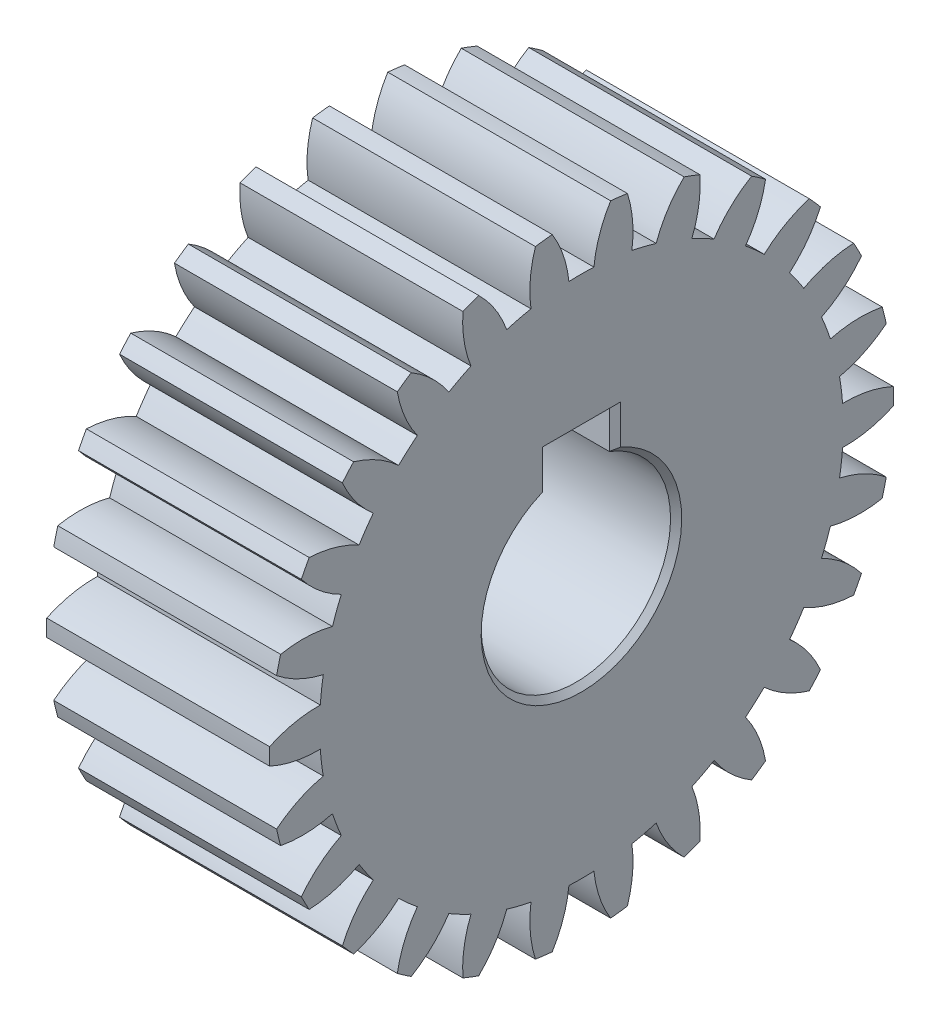
SolidWorks part; units mm, degrees
ref_plane "Plane1" through (0, 0, 0) normal (0, 0, 1) x (1, 0, 0)
ref_plane "Plane2" through (0, 0, 0) normal (0, 1, 0) x (1, 0, 0)
ref_plane "Plane3" through (0, 0, 0) normal (1, 0, 0) x (0, 0, -1)
sketch "HoldingSke" plane through (0, 0, 0) normal (0, 1, 0) x (1, 0, 0)
  line L0 (0, 0) -> (0.4494, -0.2192)
  line L1 (-15, 0) -> (100, 0) construction
  line L2 (0, 0) -> (-2.1039, 2.3779)
  line L3 (0, 0) -> (-11.863, 4.5341)
  line L4 (0, 0) -> (7.762, 3.7858)
  line L5 (0, 0) -> (-46.8476, -17.4728)
  line L6 (0, 0) -> (-16.5793, -11.1861)
  line L7 (-2.1039, 2.3779) -> (8.6586, 51.2059)
  line L8 (-76.2, 54.61) -> (-73.4, 54.61)
  line L9 (-67.7845, 28.3722) -> (-49.3413, 33.142)
  line L10 (-76.2, 71.12) -> (104.1128, 71.12)
  line L11 (0, 0) -> (-20, 0)
  line L12 (-76.2, 101.6) -> (-76.133, 101.6)
  line L13 (24.9733, 27.94) -> (52.9518, 28.4284)
  line L14 (24.9733, 27.94) -> (24.9743, 27.94)
  line L15 (24.9733, 27.94) -> (100.4006, 29.5858)
  line L16 (-63.627, -2) -> (-12.827, -2)
  circle A0 centre (0, 0) radius 8.5
  circle A1 centre (0, 0) radius 23.499
  circle A2 centre (0, 0) radius 37.5
  circle A3 centre (0, 0) radius 8.5
  dimension "Num_teeth" = 26
  dimension "Pitch_radius" = 180.3128
  dimension "Width" = 20
  dimension "Thickness" = 20
sketch "BasProSke" plane through (0, 0, 0) normal (0, 1, 0) x (1, 0, 0)
  line L0 (-10, 0) -> (60, 0) construction
  line L1 (0, 0) -> (0, 28)
  line L2 (0, 0) -> (20, 0)
  line L3 (20, 0) -> (20, 28)
  line L4 (20, 28) -> (0, 28)
  dimension "Thickness" = 20
  dimension "Diameter" = 56
revolve "Base-Revolve" add sketch "BasProSke" angle 360 about L0
sketch "TooCutSke" plane through (0, 0, 0) normal (1, 0, 0) x (0, 0, -1)
  line L1 (0, 0) -> (0, 107) construction
  line L2 (0, 0) -> (-1.6871, 25.9452) construction
  line L3 (0, 0) -> (-6.2581, 51.5402) construction
  line L4 (-1.6871, 25.9452) -> (-3.1291, 25.7701) construction
  arc A0 (1.1217, 23.4722) -> (-1.1217, 23.4722) centre (0, 0) ccw
  arc A1 (2.6361, 27.9012) -> (-2.6361, 27.9012) centre (0, 0) ccw
  circle A2 centre (0, 0) radius 26 construction
  circle A3 centre (0, 0) radius 25.1718 construction
  arc A4 (-1.1217, 23.4722) -> (-2.6361, 27.9012) centre (-11.4671, 22.4082) ccw
  arc A5 (2.6361, 27.9012) -> (1.1217, 23.4722) centre (11.4671, 22.4082) ccw
extrude "ToothCut" cut sketch "TooCutSke" along normal through all
fillet "Breaks" [suppressed] radius 0.04 tangent propagation no
fillet "RootFillets" [suppressed] radius 0.501
pattern_circular "TeethCuts" count 26 every 13.846 about axis through (-10, 0, 0) along (1, 0, 0) of "ToothCut", "RootFillets", "Breaks"
sketch "HubNeaOneSke" plane through (0, 0, 0) normal (-1, 0, 0) x (0, 0, 1)
  circle A0 centre (0, 0) radius 23.499
  dimension "Diameter" = 46.998
extrude "HubNearOne" [suppressed] add sketch "HubNeaOneSke" along normal blind 30.0001
sketch "HubNeaBotSke" plane through (0, 0, 0) normal (-1, 0, 0) x (0, 0, 1)
  circle A0 centre (0, 0) radius 23.499
  dimension "Diameter" = 46.998
extrude "HubNearBoth" [suppressed] add sketch "HubNeaBotSke" along normal blind 15
ref_plane "FarPln" through (20, 0, 0) normal (1, 0, 0) x (0, 0, -1)
sketch "HubFarSke" plane through (20, 0, 0) normal (1, 0, 0) x (0, 0, -1)
  circle A0 centre (0, 0) radius 23.499
  dimension "Diameter" = 46.998
extrude "HubFar" [suppressed] add sketch "HubFarSke" along normal blind 15
sketch "BorSke" plane through (0, 0, 0) normal (1, 0, 0) x (0, 0, -1)
  circle A0 centre (0, 0) radius 8.5
  dimension "Diameter" = 17
extrude "Bore" cut sketch "BorSke" along normal mid plane 100.0001
sketch "KeySke" plane through (0, 0, 0) normal (1, 0, 0) x (0, 0, -1)
  line L0 (-3, 0) -> (-3, 11.3)
  line L1 (-3, 11.3) -> (3, 11.3)
  line L2 (3, 11.3) -> (3, 0)
  line L3 (0, 0) -> (0, 34) construction
  line L4 (-3, 0) -> (3, 0)
  dimension "Width" = 6
extrude "Keyway" cut sketch "KeySke" along normal mid plane 100.0001
pattern_circular "Keyway2" [suppressed] count 2 every 90 about axis through (-10, 0, 0) along (1, 0, 0) reverse direction yes
chamfer "Chanfros 0.5×45°" distance 0.5 angle 45 8 edges at (0, -8.5, 0) (0, 9.6265, 3) (0, 11.3, 0) (0, 9.6265, -3) (20, 9.6265, -3) (20, 11.3, 0) (20, 9.6265, 3) (20, -8.5, 0)
equation "' \"Module@HoldingSke\" = 6.35"
equation "' \"Num_teeth@HoldingSke\" = 12"
equation "' \"Ap@HoldingSke\" =  20"
equation "' \"Ap@HoldingSke\" = 20"
equation "' \"Width@HoldingSke\" = 0.5 * 25.4"
equation "' \"Hub_dia@HoldingSke\"= 1 * 25.4"
equation "' \"Hub_dia@HoldingSke\" = 1 * 25.4"
equation "' \"Overall_len@HoldingSke\" = 1.0 * 25.4"
equation "' \"Bore@HoldingSke\" = 0.75 * 25.4"
equation "' \"T_dim@HoldingSke\" = 0.1 * 25.4"
equation "' \"Width@KeySke\" = 0.25 * 25.4"
equation "' \"Show_teeth@HoldingSke\" = 13"
equation "' \"Backlash@HoldingSke\" = 0.009 * 25.4"
equation "' \"Addendum_fac@HoldingSke\" = 1.0"
equation "' \"Dedendum_fac@HoldingSke\" = 1.25"
equation "' \"Dedendum_add@HoldingSke\" = 0.00005 * 25.4"
equation "' \"Clearance_fac@HoldingSke\" = 0.25"
equation "\"Pitch@HoldingSke\" = 1 / \"Module@HoldingSke\""
equation "\"Overcut_dia@TooCutSke\" = (\"Num_teeth@HoldingSke\" + 2 * \"Addendum_fac@HoldingSke\") / \"Pitch@HoldingSke\" + 0.002 * 25.4"
equation "\"Pitch_dia@TooCutSke\" = \"Num_teeth@HoldingSke\" / \"Pitch@HoldingSke\""
equation "\"Base_dia@TooCutSke\" = \"Num_teeth@HoldingSke\" / \"Pitch@HoldingSke\" * cos((\"Ap@HoldingSke\"  * 3.14159265 / 180))"
equation "\"Root_dia@TooCutSke\" = (\"Num_teeth@HoldingSke\" + 2) / \"Pitch@HoldingSke\" - 2 * (\"Addendum_fac@HoldingSke\" + \"Dedendum_fac@HoldingSke\") / \"Pitch@HoldingSke\" - \"Dedendum_add@HoldingSke\" * 2"
equation "\"Half_ang@TooCutSke\" = 180 / \"Num_teeth@HoldingSke\""
equation "\"Half_CT@TooCutSke\" = \"Num_teeth@HoldingSke\" / \"Pitch@HoldingSke\" * sin((3.14159265 / 2 / \"Num_teeth@HoldingSke\")) / 2 - 7 * \"Backlash@HoldingSke\" / 4"
equation "\"Flank_rad@TooCutSke\" = \"Num_teeth@HoldingSke\" / \"Pitch@HoldingSke\" / 5"
equation "\"Radius@RootFillets\" = \"Clearance_fac@HoldingSke\" / \"Pitch@HoldingSke\" + \"Dedendum_add@HoldingSke\""
equation "\"Break_rad@Breaks\" = 0.02 / \"Pitch@HoldingSke\""
equation "\"Thickness@HoldingSke\" = \"Width@HoldingSke\""
equation "\"OAL@HoldingSke\" = \"Thickness@HoldingSke\""
equation "\"MHD@HoldingSke\" = (\"Num_teeth@HoldingSke\" + 2) / \"Pitch@HoldingSke\" - 2 * (\"Addendum_fac@HoldingSke\" + \"Dedendum_fac@HoldingSke\")  / \"Pitch@HoldingSke\" - \"Dedendum_add@HoldingSke\" * 2"
equation "\"MBD@HoldingSke\" = (\"Num_teeth@HoldingSke\" + 2) / \"Pitch@HoldingSke\" - 2 * (\"Addendum_fac@HoldingSke\" + \"Dedendum_fac@HoldingSke\")  / \"Pitch@HoldingSke\" - \"Dedendum_add@HoldingSke\" * 2 - 0.002 * 25.4"
equation "\"MHD@HoldingSke\" = ((sgn( \"MHD@HoldingSke\" - \"Hub_dia@HoldingSke\" )-1)*( \"MHD@HoldingSke\" - \"Hub_dia@HoldingSke\" ))/-2+ \"Hub_dia@HoldingSke\""
equation "\"MBD@HoldingSke\" = ((sgn( \"MBD@HoldingSke\" - \"Bore@HoldingSke\" )-1)*( \"MBD@HoldingSke\" - \"Bore@HoldingSke\" ))/-2+ \"Bore@HoldingSke\""
equation "\"OAL@HoldingSke\" = ((sgn( \"OAL@HoldingSke\" - \"Overall_len@HoldingSke\" )+1)*( \"OAL@HoldingSke\" - \"Overall_len@HoldingSke\" ))/2 + \"Overall_len@HoldingSke\" + 0.000002 * 25.4"
equation "\"Num_teeth@TeethCuts\" = int( \"Show_teeth@HoldingSke\" ) + 1"
equation "\"Num_teeth@TeethCuts\" = ((sgn( \"Num_teeth@TeethCuts\" - \"Num_teeth@HoldingSke\" )-1)*( \"Num_teeth@TeethCuts\" - \"Num_teeth@HoldingSke\" ))/-2+ \"Num_teeth@HoldingSke\""
equation "\"Num_teeth@TeethCuts\" = ((sgn( \"Num_teeth@TeethCuts\" - 2.0)+1)*( \"Num_teeth@TeethCuts\" - 2.0))/2 +2.0"
equation "\"Angle@TeethCuts\" = 360.0 / \"Num_teeth@HoldingSke\""
equation "\"Diameter@BasProSke\" = (\"Num_teeth@HoldingSke\" + 2 * \"Addendum_fac@HoldingSke\") / \"Pitch@HoldingSke\""
equation "\"Thickness@BasProSke\"  = \"Thickness@HoldingSke\""
equation "' \"Fillet_rad@BasProSke\" =  \"Thickness@HoldingSke\" * 0.05"
equation "' \"Fillet_rad@BasProSke\" = \"Thickness@HoldingSke\" * 0.05"
equation "\"MHD@HoldingSke\" = ((sgn( \"MHD@HoldingSke\" - \"Root_dia@TooCutSke\" )-1)*( \"MHD@HoldingSke\" - \"Root_dia@TooCutSke\" ))/-2+ \"Root_dia@TooCutSke\""
equation "\"Diameter@HubNeaOneSke\" = \"MHD@HoldingSke\""
equation "\"Length@HubNearOne\" = \"OAL@HoldingSke\" - \"Thickness@BasProSke\""
equation "\"Diameter@HubNeaBotSke\" = \"MHD@HoldingSke\""
equation "\"Length@HubNearBoth\" = ( \"OAL@HoldingSke\" - \"Thickness@BasProSke\" ) / 2.0"
equation "\"Thickness@FarPln\" = \"Thickness@BasProSke\""
equation "\"Diameter@HubFarSke\" = \"MHD@HoldingSke\""
equation "\"Length@HubFar\" = ( \"OAL@HoldingSke\" - \"Thickness@BasProSke\" ) / 2.0"
equation "\"Diameter@BorSke\" = \"MBD@HoldingSke\""
equation "\"D1@Bore\" = \"OAL@HoldingSke\" * 2.0"
equation "\"D1@Keyway\" = \"OAL@HoldingSke\" * 2.0"
equation "\"Offset@KeySke\" = \"T_dim@HoldingSke\" + \"MBD@HoldingSke\" / 2.0"
